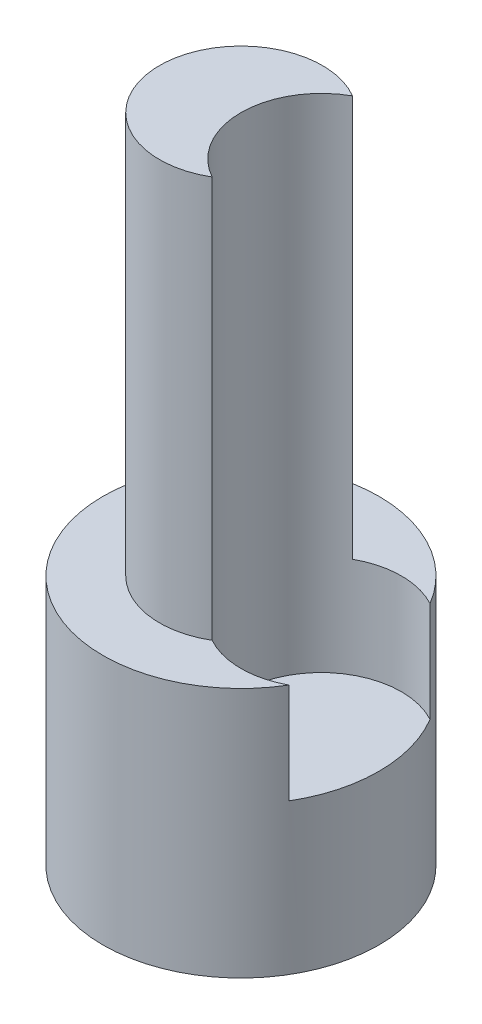
SolidWorks part; units mm, degrees
ref_plane "Front Plane" through (0, 0, 0) normal (0, 0, 1) x (1, 0, 0)
ref_plane "Top Plane" through (0, 0, 0) normal (0, 1, 0) x (1, 0, 0)
ref_plane "Right Plane" through (0, 0, 0) normal (1, 0, 0) x (0, 0, -1)
sketch "Sketch1" plane through (0, 0, 0) normal (0, 1, 0) x (1, 0, 0)
  circle A0 centre (0, 0) radius 1.625
  circle A1 centre (0, 0) radius 2.75
  circle A2 centre (1.6, 0) radius 1.6
  point P6 (0, 0)
  point P7 (0, 0)
  dimension "D1" = 5.5
  dimension "D2" = 3.25
  dimension "D3" = 3.2
extrude "Boss-Extrude1" add sketch "Sketch1" along normal blind 5 contours A1 A0 | A0 A2 region at (1.9511, 0, 0) region at (-1.7001, 0, 0)
extrude "Boss-Extrude3" add sketch "Sketch1<4>" along normal blind 13 contours A0 A2 | A0 A2 region at (0.814, 0, 0) region at (-0.5186, 0, 0)
sketch "Sketch1<4>" plane through (0, 0, 0) normal (0, 1, 0) x (1, 0, 0) same geometry as "Sketch1"
extrude "Cut-Extrude3" cut sketch "Sketch1<6>" against normal blind 10 from surface contours A0 A2 | A0 A2 region at (0.814, 0, 0) region at (1.9511, 0, 0) starting at face at (0, 13, 1.625)
sketch "Sketch1<6>" plane through (0, 0, 0) normal (0, 1, 0) x (1, 0, 0) same geometry as "Sketch1"
